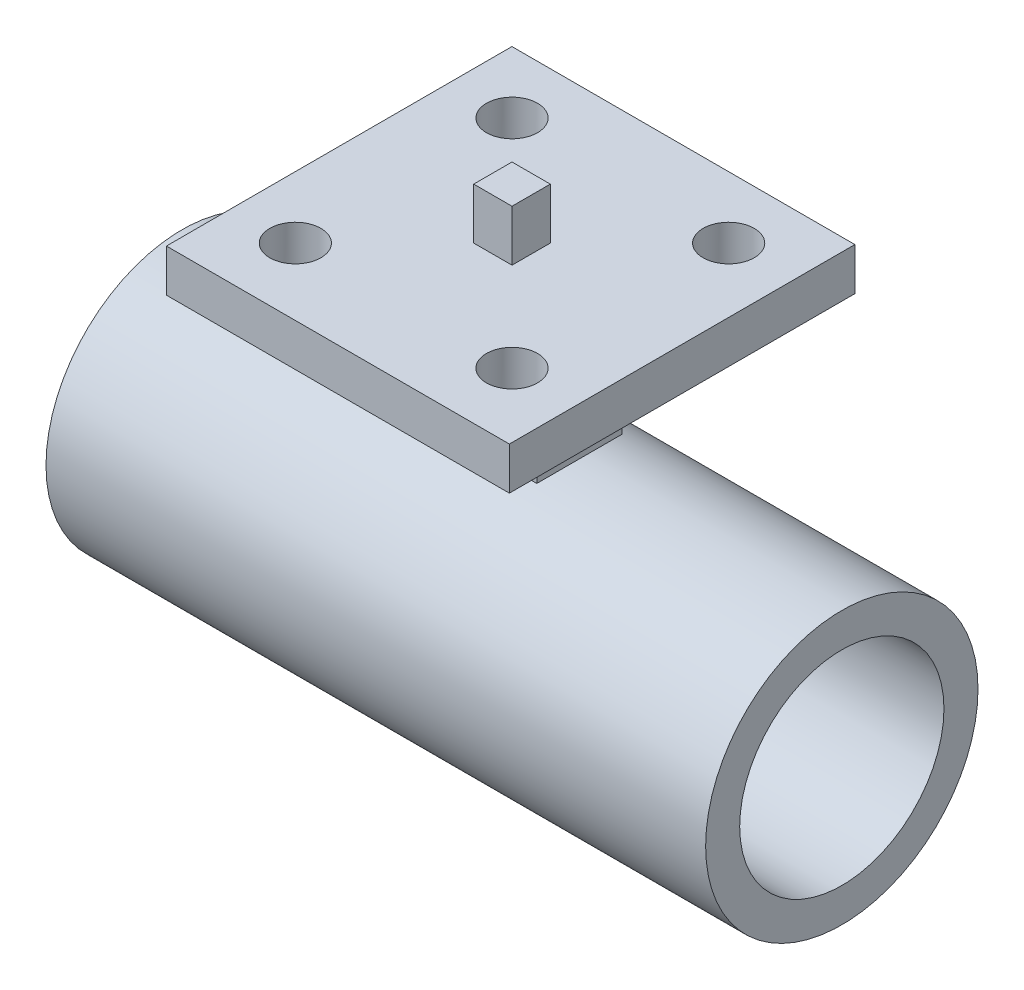
SolidWorks part; units mm, degrees
ref_plane "Płaszczyzna przednia" through (0, 0, 0) normal (0, 0, 1) x (1, 0, 0)
ref_plane "Płaszczyzna górna" through (0, 0, 0) normal (0, 1, 0) x (1, 0, 0)
ref_plane "Płaszczyzna prawa" through (0, 0, 0) normal (1, 0, 0) x (0, 0, -1)
sketch "Szkic1" plane through (0, 0, 0) normal (0, 0, 1) x (1, 0, 0)
  line L0 (0, 0) -> (77.5, 0)
  line L1 (0, 0) -> (0, 12)
  line L2 (77.5, 0) -> (77.5, 12)
  line L3 (38.75, 0) -> (38.75, 34)
  line L4 (38.75, 34) -> (22.75, 34)
  line L5 (38.75, 34) -> (54.75, 34)
  line L6 (22.75, 34) -> (22.75, 29)
  line L7 (22.75, 29) -> (54.75, 29)
  line L8 (54.75, 29) -> (54.75, 34)
  line L9 (38.75, 29) -> (30.8336, 29)
  line L10 (0, 12) -> (0, 16)
  line L11 (0, 16) -> (77.5, 16)
  line L12 (77.5, 16) -> (77.5, 12)
  line L13 (77.5, 12) -> (0, 12)
  line L14 (30.8336, 29) -> (30.8336, 16)
  line L15 (46.6664, 29) -> (46.6664, 16)
extrude "Dodanie-wyciągnięcie1" add sketch "Szkic1" along normal blind 16 and the other way blind 16 contours L15 L7 L3 L11 | L7 L14 L11 L3 | L6 L7 L3 L4 | L7 L8 L5 L3 region at (34.7918, 22.5, 0) region at (42.7082, 22.5, 0) region at (30.75, 31.5, 0) region at (46.75, 31.5, 0)
sketch "Szkic2" plane through (0, 34, 0) normal (0, 1, 0) x (1, 0, 0)
  line L0 (38.75, 16) -> (38.75, 0)
  line L1 (38.75, 0) -> (51.4779, 12.7279)
  line L2 (22.75, 16) -> (54.75, 16) construction
  circle A0 centre (51.4779, 12.7279) radius 3
  circle A1 centre (38.75, 0) radius 18
  circle A2 centre (38.75, 0) radius 18
  circle A3 centre (51.4779, -12.7279) radius 3
  circle A4 centre (38.75, 0) radius 18
  circle A5 centre (26.0221, -12.7279) radius 3
  circle A6 centre (38.75, 0) radius 18
  circle A7 centre (26.0221, 12.7279) radius 3
  point P19 (38.75, 0)
  dimension "D1" = 4
extrude "Wytnij-wyciągnięcie1" cut sketch "Szkic2" against normal blind 15 contours A6 A7 | A6 A7 | A1 A0 | L1 A1 A0 | A0 A1 L1 | A2 A3 | A2 A3 | A4 A5 | A4 A5 region at (49.6715, 34, -12.6715) region at (51.4215, 34, -10.9215) region at (52.3456, 34, -13.5956) region at (26.9535, 34, -11.7965) region at (25.1544, 34, -13.5956) region at (52.3456, 34, 13.5956) region at (50.5465, 34, 11.7965) region at (26.9535, 34, 11.7965) region at (25.1544, 34, 13.5956)
sketch "Szkic3" plane through (0, 34, 0) normal (0, 1, 0) x (1, 0, 0)
  line L0 (38.75, 16) -> (38.75, 0)
  line L1 (22.75, 16) -> (54.75, 16) construction
  line L3 (36.5, -2.2497) -> (41, -2.2497)
  line L4 (36.5, -2.2497) -> (36.5, 2.2497)
  line L5 (36.5, 2.2497) -> (41, 2.2497)
  line L6 (41, -2.2497) -> (41, 2.2497)
  line L7 (36.5, -2.2497) -> (41, 2.2497) construction
  line L8 (36.5, 2.2497) -> (41, -2.2497) construction
extrude "Dodanie-wyciągnięcie2" add sketch "Szkic3" along normal blind 6 contours L3 L6 L5 L4 region at (36.5637, 34, 0)
sketch "Szkic4" plane through (0, 0, 0) normal (0, 0, 1) x (1, 0, 0)
  line L0 (0, 0) -> (77.5, 0)
  line L1 (77.5, 0) -> (77.5, 12)
  line L2 (77.5, 12) -> (0, 12)
  line L3 (0, 12) -> (0, 0)
  line L4 (0, 12) -> (0, 16)
  line L5 (0, 16) -> (30.8336, 16)
  line L6 (46.6664, 16) -> (77.5, 16)
  line L7 (77.5, 16) -> (77.5, 12)
  line L8 (30.8336, 16) -> (46.6664, 16)
revolve "Obrót2" add sketch "Szkic4" angle 360 about L0 region at (38.75, 14, 0)
sketch "Szkic5" plane through (0, 0, 16) normal (0, 0, 1) x (1, 0, 0)
  line L0 (46.6664, 29) -> (46.6664, 16) construction
  line L1 (30.8336, 16) -> (46.6664, 16)
  line L2 (30.8336, 16) -> (30.8336, 29)
  line L3 (30.8336, 29) -> (46.6664, 29)
  line L4 (46.6664, 16) -> (46.6664, 29)
  line L5 (46.6664, 29) -> (54.75, 29) construction
extrude "Wytnij-wyciągnięcie2" cut sketch "Szkic5" against normal blind 11
sketch "Szkic6" plane through (0, 0, -16) normal (0, 0, -1) x (-1, 0, 0)
  line L1 (-46.6664, 16) -> (-30.8336, 16)
  line L2 (-46.6664, 16) -> (-46.6664, 29)
  line L3 (-46.6664, 29) -> (-30.8336, 29)
  line L4 (-30.8336, 16) -> (-30.8336, 29)
extrude "Wytnij-wyciągnięcie3" cut sketch "Szkic6" against normal blind 11
sketch "Szkic7" plane through (0, 34, 0) normal (0, 1, 0) x (1, 0, 0)
  line L1 (22.75, 16) -> (18.7499, 16)
  line L2 (22.75, 16) -> (22.75, 19.9925)
  line L3 (22.75, 19.9925) -> (18.7499, 19.9925)
  line L4 (18.7499, 16) -> (18.7499, 19.9925)
  line L5 (18.7499, 19.9925) -> (59.0416, 19.9925)
  line L6 (18.7499, 19.9925) -> (18.7499, -20.6022)
  line L7 (18.7499, -20.6022) -> (59.0416, -20.6022)
  line L8 (59.0416, 19.9925) -> (59.0416, -20.6022)
  line M1 (22.75, 16) -> (22.75, -16)
  line M2 (22.75, -16) -> (54.75, -16)
  line M3 (54.75, -16) -> (54.75, 16)
  line M4 (54.75, 16) -> (22.75, 16)
extrude "Dodanie-wyciągnięcie3" add sketch "Szkic7" against normal blind 5 contours L8 L5 L2 L1 L6 L7 M4 M3 M2 M1 | L4 L1 L2 L3 region at (23.322, 34, -17.9962) region at (20.7499, 34, -17.9962)
